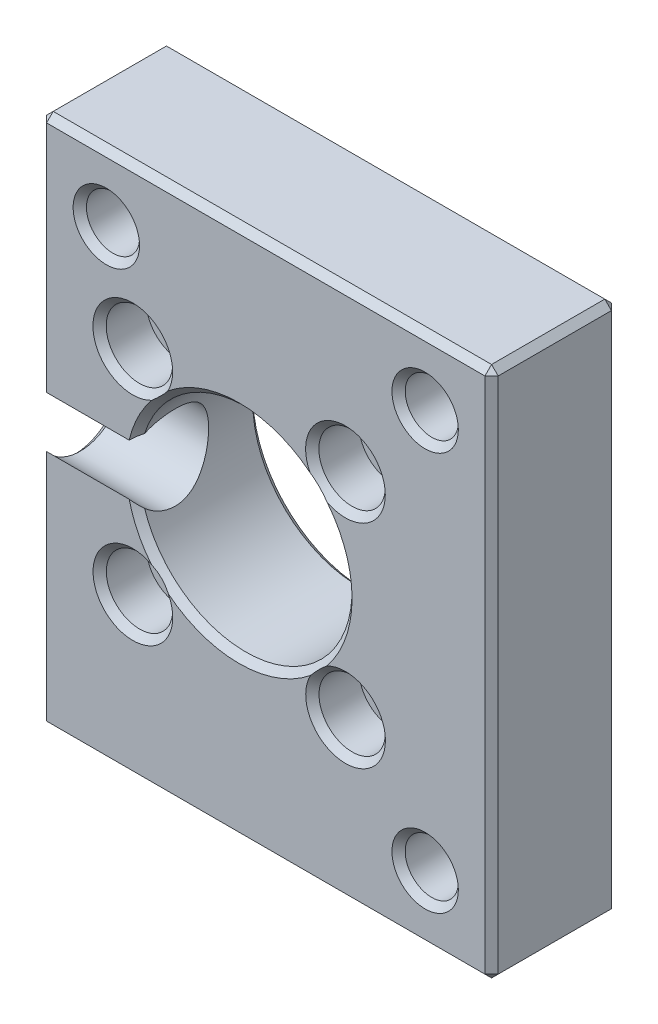
SolidWorks part; units mm, degrees
ref_plane "Front Plane" through (0, 0, 0) normal (0, 0, 1) x (1, 0, 0)
ref_plane "Top Plane" through (0, 0, 0) normal (0, 1, 0) x (1, 0, 0)
ref_plane "Right Plane" through (0, 0, 0) normal (1, 0, 0) x (0, 0, -1)
sketch "Sketch2" plane through (0, 0, 0) normal (0, 0, 1) x (1, 0, 0)
  line L0 (10, -8.01) -> (10, 8.01)
  line L1 (8.01, 10) -> (-8.01, 10)
  line L2 (-10, 8.01) -> (-10, -8.01)
  line L3 (-8.01, -10) -> (8.01, -10)
  line L5 (-11, 20) -> (19, 20)
  line L7 (-11, -20) -> (19, -20)
  line L8 (19, 20) -> (19, -20)
  line L9 (-11, -20) -> (-15, -20)
  line L11 (-11, 20) -> (-15, 20)
  line L12 (-15, -20) -> (-15, 20)
  arc A0 (10, 8.01) -> (8.01, 10) centre (8.01, 8.01) ccw
  arc A1 (-8.01, 10) -> (-10, 8.01) centre (-8.01, 8.01) ccw
  arc A2 (-10, -8.01) -> (-8.01, -10) centre (-8.01, -8.01) ccw
  arc A3 (8.01, -10) -> (10, -8.01) centre (8.01, -8.01) ccw
  circle A4 centre (8, -8) radius 1.25
  circle A5 centre (8, 8) radius 1.25
  circle A6 centre (-8, 8) radius 1.25
  circle A7 centre (-8, -8) radius 1.25
  circle A8 centre (0, 0) radius 8
  circle A9 centre (-10, 15) radius 3.9687
  circle A10 centre (14, 15) radius 3.9687
  circle A11 centre (14, -15) radius 3.9688
  circle A12 centre (-10, 15) radius 2
  circle A13 centre (14, 15) radius 2
  circle A14 centre (14, -15) radius 2
  circle A15 centre (-10, 15) radius 3.25
  circle A16 centre (14, -15) radius 3.25
  circle A17 centre (14, 15) radius 3.25
  dimension "D3" = 10
  dimension "D4" = 10
  dimension "D6" = 16
  dimension "D7" = 2.5
  dimension "D8" = 1.99
  dimension "D15" = 7.9375
  dimension "D16" = 4
  dimension "D17" = 7.9375
  dimension "D18" = 4
  dimension "D19" = 7.9375
  dimension "D20" = 4
  dimension "D21" = 6.5
  dimension "D22" = 6.5
  dimension "D23" = 6.5
  dimension "D24" = 34
  dimension "D1" = 40
  dimension "D2" = 30
  dimension "D5" = 16.02
  dimension "D9" = 8
  dimension "D10" = 19
  dimension "D11" = 8
  dimension "D12" = 8
  dimension "D13" = 20
  dimension "D14" = 8
  dimension "D25" = 5
  dimension "D26" = 5
  dimension "D27" = 5
  dimension "D28" = 29
  dimension "D29" = 5
  dimension "D30" = 5
extrude "Boss-Extrude1" add sketch "Sketch2" along normal blind 9.525
sketch "Sketch3" plane through (0, 0, 0) normal (0, 0, -1) x (-1, 0, 0)
  line L1 (11, 20) -> (-19, 20) construction
  line L2 (-19, 20) -> (-19, -20) construction
  line L3 (11, -20) -> (-19, -20) construction
  line L4 (-10, 8.01) -> (-10, -8.01)
  line L5 (8.01, 10) -> (-8.01, 10)
  line L6 (10, -8.01) -> (10, 8.01)
  line L7 (-8.01, -10) -> (8.01, -10)
  line L8 (-10, 8.01) -> (-10, -8.01)
  line L9 (8.01, 10) -> (-8.01, 10)
  line L10 (10, -8.01) -> (10, 8.01)
  line L11 (-8.01, -10) -> (8.01, -10)
  line L12 (11, 20) -> (-19, 20)
  line L13 (-19, 20) -> (-19, -20)
  line L14 (-19, -20) -> (11, -20)
  line L15 (11, -20) -> (15, -20)
  line L16 (11, 20) -> (-19, 20)
  line L17 (-19, 20) -> (-19, -20)
  line L18 (-19, -20) -> (11, -20)
  line L19 (11, -20) -> (15, -20)
  line L20 (11, -20) -> (15, -20) construction
  line L21 (15, -20) -> (15, 20) construction
  line L22 (11, 20) -> (15, 20) construction
  line L24 (-10, -8.01) -> (-10, 8.01) construction
  line L25 (-8.01, 10) -> (8.01, 10) construction
  line L26 (10, 8.01) -> (10, -8.01) construction
  line L27 (8.01, -10) -> (-8.01, -10) construction
  line L29 (11, 20) -> (-19, 20)
  line L30 (-19, 20) -> (-19, -20)
  line L31 (11, -20) -> (-19, -20)
  line L32 (11, -20) -> (15, -20)
  line L33 (15, -20) -> (15, 20)
  line L34 (11, 20) -> (15, 20)
  line L36 (-10, -8.01) -> (-10, 8.01)
  line L37 (-8.01, 10) -> (8.01, 10)
  line L38 (10, 8.01) -> (10, -8.01)
  line L39 (8.01, -10) -> (-8.01, -10)
  line L46 (15, -20) -> (15, 20)
  line L47 (15, -20) -> (15, 20)
  line L48 (15, 20) -> (11, 20)
  line L49 (15, 20) -> (11, 20)
  arc A0 (-8.01, 10) -> (-10, 8.01) centre (-8.01, 8.01) ccw construction
  circle A1 centre (-14, 15) radius 3.9687
  circle A2 centre (-14, 15) radius 3.9688
  circle A3 centre (10, 15) radius 3.9687
  arc A4 (-8.01, 10) -> (-10, 8.01) centre (-8.01, 8.01) ccw
  arc A5 (10, 8.01) -> (8.01, 10) centre (8.01, 8.01) ccw
  arc A6 (8.01, -10) -> (10, -8.01) centre (8.01, -8.01) ccw
  arc A7 (-10, -8.01) -> (-8.01, -10) centre (-8.01, -8.01) ccw
  arc A8 (-8.01, 10) -> (-10, 8.01) centre (-8.01, 8.01) ccw
  arc A9 (10, 8.01) -> (8.01, 10) centre (8.01, 8.01) ccw
  arc A10 (8.01, -10) -> (10, -8.01) centre (8.01, -8.01) ccw
  arc A11 (-10, -8.01) -> (-8.01, -10) centre (-8.01, -8.01) ccw
  circle A12 centre (10, 15) radius 3.9688
  circle A13 centre (0, 0) radius 8
  circle A14 centre (0, 0) radius 8
  circle A15 centre (8, -8) radius 1.25
  circle A16 centre (8, -8) radius 1.25
  circle A17 centre (8, 8) radius 1.25
  circle A18 centre (8, 8) radius 1.25
  circle A19 centre (-8, 8) radius 1.25
  circle A20 centre (-8, 8) radius 1.25
  circle A21 centre (-8, -8) radius 1.25
  circle A22 centre (-8, -8) radius 1.25
  circle A23 centre (-14, 15) radius 3.25
  circle A24 centre (-14, 15) radius 3.25
  circle A25 centre (-14, -15) radius 3.25
  circle A26 centre (-14, -15) radius 3.25
  circle A27 centre (10, 15) radius 3.25
  circle A28 centre (10, 15) radius 3.25
  circle A29 centre (-14, -15) radius 2
  circle A30 centre (-14, -15) radius 2
  circle A31 centre (-14, 15) radius 2
  circle A32 centre (-14, 15) radius 2
  circle A33 centre (10, 15) radius 2
  circle A34 centre (10, 15) radius 2
  circle A35 centre (-14, -15) radius 3.9688
  circle A36 centre (-14, -15) radius 3.9688
  arc A37 (10, 8.01) -> (8.01, 10) centre (8.01, 8.01) ccw construction
  arc A38 (8.01, -10) -> (10, -8.01) centre (8.01, -8.01) ccw construction
  arc A39 (-10, -8.01) -> (-8.01, -10) centre (-8.01, -8.01) ccw construction
  circle A40 centre (-14, 15) radius 3.9687 construction
  circle A41 centre (10, 15) radius 3.9687 construction
  circle A42 centre (0, 0) radius 8 construction
  circle A43 centre (8, -8) radius 1.25 construction
  circle A44 centre (8, 8) radius 1.25 construction
  circle A45 centre (-8, 8) radius 1.25 construction
  circle A46 centre (-8, -8) radius 1.25 construction
  circle A47 centre (-14, 15) radius 3.25 construction
  circle A48 centre (-14, -15) radius 3.25 construction
  circle A49 centre (10, 15) radius 3.25 construction
  circle A50 centre (-14, -15) radius 2 construction
  circle A51 centre (-14, 15) radius 2 construction
  circle A52 centre (10, 15) radius 2 construction
  circle A53 centre (-14, -15) radius 3.9688 construction
  arc A54 (-8.01, 10) -> (-10, 8.01) centre (-8.01, 8.01) ccw
  arc A55 (10, 8.01) -> (8.01, 10) centre (8.01, 8.01) ccw
  arc A56 (8.01, -10) -> (10, -8.01) centre (8.01, -8.01) ccw
  arc A57 (-10, -8.01) -> (-8.01, -10) centre (-8.01, -8.01) ccw
  circle A58 centre (-14, 15) radius 3.9688
  circle A59 centre (10, 15) radius 3.9688
  circle A60 centre (0, 0) radius 8
  circle A61 centre (8, -8) radius 1.25
  circle A62 centre (8, 8) radius 1.25
  circle A63 centre (-8, 8) radius 1.25
  circle A64 centre (-8, -8) radius 1.25
  circle A65 centre (-14, 15) radius 3.25
  circle A66 centre (-14, -15) radius 3.25
  circle A67 centre (10, 15) radius 3.25
  circle A68 centre (-14, -15) radius 2
  circle A69 centre (-14, 15) radius 2
  circle A70 centre (10, 15) radius 2
  circle A71 centre (-14, -15) radius 3.9688
  dimension "D1" = 0
  dimension "D2" = 0
  dimension "D3" = 0
  dimension "D4" = 0
  dimension "D5" = 0
  dimension "D6" = 0
  dimension "D7" = 0
  dimension "D8" = 0
  dimension "D9" = 0
  dimension "D10" = 0
  dimension "D11" = 0
  dimension "D12" = 0
  dimension "D13" = 0
  dimension "D14" = 0
  dimension "D15" = 0
  dimension "D16" = 0
extrude "Cut-Extrude1" cut sketch "Sketch3" against normal through all contours A14
sketch "Sketch4" plane through (0, 0, 9.525) normal (0, 0, 1) x (1, 0, 0)
  line L4 (19, -20) -> (19, 20)
  line L5 (19, 20) -> (-15, 20)
  line L6 (-15, 20) -> (-15, -20)
  line L7 (-15, -20) -> (19, -20)
  line L8 (19, -20) -> (19, 20)
  line L9 (19, 20) -> (-15, 20)
  line L11 (-15, -20) -> (19, -20)
  line L12 (10, -8.01) -> (10, 8.01)
  line L13 (8.01, 10) -> (-8.01, 10)
  line L14 (-10, 8.01) -> (-10, -8.01)
  line L15 (-8.01, -10) -> (8.01, -10)
  line L16 (10, -8.01) -> (10, 8.01)
  line L17 (8.01, 10) -> (-8.01, 10)
  line L18 (-10, 8.01) -> (-10, -8.01)
  line L19 (-8.01, -10) -> (8.01, -10)
  line L20 (19, 20) -> (-15, 20)
  line L21 (19, -20) -> (19, 20)
  line L22 (-15, -20) -> (19, -20)
  line L23 (-15, -20) -> (-11, -20)
  line L24 (19, 20) -> (-15, 20)
  line L25 (19, -20) -> (19, 20)
  line L26 (-15, -20) -> (19, -20)
  line L28 (-15, 20) -> (-15, -20)
  line L31 (-15, -20) -> (-11, -20)
  line L32 (-15, 20) -> (-15, -20)
  line L33 (-15, 20) -> (-15, -20)
  line L34 (-11, 20) -> (-15, 20)
  line L35 (-11, 20) -> (-15, 20)
  circle A0 centre (-8, -8) radius 2.5
  circle A1 centre (14, 15) radius 3.9687
  circle A2 centre (14, 15) radius 3.9688
  circle A3 centre (-10, 15) radius 3.9687
  arc A4 (10, 8.01) -> (8.01, 10) centre (8.01, 8.01) ccw
  arc A5 (-8.01, 10) -> (-10, 8.01) centre (-8.01, 8.01) ccw
  arc A6 (-10, -8.01) -> (-8.01, -10) centre (-8.01, -8.01) ccw
  arc A7 (8.01, -10) -> (10, -8.01) centre (8.01, -8.01) ccw
  arc A8 (10, 8.01) -> (8.01, 10) centre (8.01, 8.01) ccw
  arc A9 (-8.01, 10) -> (-10, 8.01) centre (-8.01, 8.01) ccw
  arc A10 (-10, -8.01) -> (-8.01, -10) centre (-8.01, -8.01) ccw
  arc A11 (8.01, -10) -> (10, -8.01) centre (8.01, -8.01) ccw
  circle A12 centre (-10, 15) radius 3.9688
  circle A13 centre (0, 0) radius 8
  circle A14 centre (0, 0) radius 8
  circle A15 centre (-8, -8) radius 1.25
  circle A16 centre (-8, -8) radius 1.25
  circle A17 centre (-8, 8) radius 1.25
  circle A18 centre (-8, 8) radius 1.25
  circle A19 centre (8, 8) radius 1.25
  circle A20 centre (8, 8) radius 1.25
  circle A21 centre (8, -8) radius 1.25
  circle A22 centre (8, -8) radius 1.25
  circle A23 centre (14, 15) radius 3.25
  circle A24 centre (14, 15) radius 3.25
  circle A25 centre (14, -15) radius 3.25
  circle A26 centre (14, -15) radius 3.25
  circle A27 centre (-10, 15) radius 3.25
  circle A28 centre (-10, 15) radius 3.25
  circle A29 centre (14, -15) radius 2
  circle A30 centre (14, -15) radius 2
  circle A31 centre (14, 15) radius 2
  circle A32 centre (14, 15) radius 2
  circle A33 centre (-10, 15) radius 2
  circle A34 centre (-10, 15) radius 2
  circle A35 centre (14, -15) radius 3.9688
  circle A36 centre (14, -15) radius 3.9688
  circle A37 centre (-8.01, 8.01) radius 2.5
  circle A38 centre (8, 8) radius 2.5
  circle A39 centre (8.01, -8.01) radius 2.5
  circle M9 centre (-8, -8) radius 1.25
  circle M10 centre (-8, 8) radius 1.25
  circle M11 centre (8, 8) radius 1.25
  circle M12 centre (8, -8) radius 1.25
  dimension "D18" = 5
  dimension "D19" = 5
  dimension "D20" = 5
  dimension "D21" = 5
  dimension "D1" = 0
  dimension "D2" = 0
  dimension "D3" = 0
  dimension "D4" = 0
  dimension "D5" = 0
  dimension "D6" = 0
  dimension "D7" = 0
  dimension "D8" = 0
  dimension "D9" = 0
  dimension "D10" = 0
  dimension "D11" = 0
  dimension "D12" = 0
  dimension "D13" = 0
  dimension "D14" = 0
  dimension "D15" = 0
  dimension "D16" = 0
  dimension "D17" = 0
sketch "Sketch9" plane through (-15, 0, 0) normal (-1, 0, 0) x (0, 0, 1)
  line L0 (0, -20) -> (0, 20) construction
  circle A0 centre (7, 0) radius 3.175
  dimension "D2" = 6.35
  dimension "D1" = 7
extrude "Cut-Extrude8" cut sketch "Sketch9" against normal blind 15
extrude "Cut-Extrude5" cut sketch "Sketch4" against normal blind 3.525 contours L17 A37 L18 A9 | L18 A37 L17 A9 M10 | L17 A38 L16 A8 M11 | L16 A38 L17 A8 | A10 L18 A0 L19 | L18 A10 L19 A0 M9 | L19 A39 L16 A11 | L16 A39 L19 A11 M12 | A20
sketch "Sketch7" plane through (0, 0, 9.525) normal (0, 0, 1) x (1, 0, 0)
  line L1 (-15, -20) -> (19, -20) construction
  line L2 (-15, -20) -> (19, -20) construction
  line L4 (19, 20) -> (-15, 20) construction
  line L5 (19, 20) -> (-15, 20) construction
  line L6 (19, -20) -> (19, 20) construction
  line L7 (-15, -1.9248) -> (-15, -20)
  line L8 (-15, -1.9248) -> (-15, -20)
  line L10 (-15, -20) -> (19, -20)
  line L11 (19, -20) -> (19, 20)
  line L12 (19, 20) -> (-15, 20)
  line L17 (-15, -20) -> (19, -20)
  line L18 (19, -20) -> (19, 20)
  line L19 (19, 20) -> (-15, 20)
  line L21 (19, -20) -> (19, 20) construction
  line L22 (10, -8.01) -> (10, 8.01) construction
  line L23 (8.01, 10) -> (-8.01, 10) construction
  line L24 (-10, 8.01) -> (-10, -8.01) construction
  line L25 (-8.01, -10) -> (8.01, -10) construction
  line L27 (-15, -20) -> (19, -20)
  line L28 (-15, -20) -> (19, -20)
  line L30 (19, 20) -> (-15, 20)
  line L31 (19, 20) -> (-15, 20)
  line L32 (19, -20) -> (19, 20)
  line L33 (19, -20) -> (19, 20)
  line L34 (10, -8.01) -> (10, 8.01)
  line L35 (8.01, 10) -> (-8.01, 10)
  line L36 (-10, 8.01) -> (-10, -8.01)
  line L37 (-8.01, -10) -> (8.01, -10)
  line L39 (-15, 1.9248) -> (-7.765, 1.9248)
  line L40 (-15, 1.9248) -> (-7.765, 1.9248)
  line L41 (-7.765, -1.9248) -> (-15, -1.9248)
  line L42 (-7.765, -1.9248) -> (-15, -1.9248)
  line L43 (-15, 20) -> (-15, 1.9248)
  line L44 (-15, 20) -> (-15, 1.9248)
  arc A0 (10, 8.01) -> (8.01, 10) centre (8.01, 8.01) ccw construction
  arc A2 (-7.765, -1.9248) -> (-7.765, 1.9248) centre (0, 0) ccw
  arc A3 (-8.01, 10) -> (-10, 8.01) centre (-8.01, 8.01) ccw construction
  arc A4 (-10, -8.01) -> (-8.01, -10) centre (-8.01, -8.01) ccw construction
  arc A5 (8.01, -10) -> (10, -8.01) centre (8.01, -8.01) ccw construction
  circle A6 centre (-8, -8) radius 1.25 construction
  circle A7 centre (0, 0) radius 8 construction
  circle A8 centre (-10, 15) radius 3.9688 construction
  circle A9 centre (14, 15) radius 3.9688 construction
  circle A10 centre (-10, 15) radius 3.25 construction
  circle A11 centre (14, -15) radius 3.25 construction
  circle A12 centre (14, 15) radius 3.25 construction
  circle A13 centre (8, -8) radius 1.25 construction
  circle A14 centre (8, 8) radius 1.25 construction
  circle A15 centre (-8, 8) radius 1.25 construction
  circle A16 centre (8.01, -8.01) radius 2.5 construction
  circle A17 centre (8, 8) radius 2.5 construction
  circle A18 centre (-8.01, 8.01) radius 2.5 construction
  circle A19 centre (14, -15) radius 3.9688 construction
  circle A20 centre (-10, 15) radius 2 construction
  circle A21 centre (14, 15) radius 2 construction
  circle A22 centre (14, -15) radius 2 construction
  circle A23 centre (-8, -8) radius 2.5 construction
  arc A24 (10, 8.01) -> (8.01, 10) centre (8.01, 8.01) ccw
  arc A25 (-8.01, 10) -> (-10, 8.01) centre (-8.01, 8.01) ccw
  arc A26 (-10, -8.01) -> (-8.01, -10) centre (-8.01, -8.01) ccw
  arc A27 (8.01, -10) -> (10, -8.01) centre (8.01, -8.01) ccw
  circle A28 centre (-8, -8) radius 1.25
  circle A29 centre (0, 0) radius 8
  circle A30 centre (-10, 15) radius 3.9688
  circle A31 centre (14, 15) radius 3.9688
  circle A32 centre (-10, 15) radius 3.25
  circle A33 centre (14, -15) radius 3.25
  circle A34 centre (14, 15) radius 3.25
  circle A35 centre (8, -8) radius 1.25
  circle A36 centre (8, 8) radius 1.25
  circle A37 centre (-8, 8) radius 1.25
  circle A38 centre (8.01, -8.01) radius 2.5
  circle A39 centre (8, 8) radius 2.5
  circle A40 centre (-8.01, 8.01) radius 2.5
  circle A41 centre (14, -15) radius 3.9688
  circle A42 centre (-10, 15) radius 2
  circle A43 centre (14, 15) radius 2
  circle A44 centre (14, -15) radius 2
  circle A45 centre (-8, -8) radius 2.5
  arc A46 (-7.765, -1.9248) -> (-7.765, 1.9248) centre (0, 0) ccw
  dimension "D1" = 0
extrude "Cut-Extrude6" cut sketch "Sketch7" against normal through all contours A42 | A43 | A44
sketch "Sketch8" plane through (0, 0, 0) normal (0, 0, -1) x (-1, 0, 0)
  line L4 (-10, 8.01) -> (-10, -8.01)
  line L5 (8.01, 10) -> (-8.01, 10)
  line L6 (10, -8.01) -> (10, 8.01)
  line L7 (-8.01, -10) -> (8.01, -10)
  line L8 (-10, 8.01) -> (-10, -8.01)
  line L9 (8.01, 10) -> (-8.01, 10)
  line L10 (10, -8.01) -> (10, 8.01)
  line L11 (-8.01, -10) -> (8.01, -10)
  line L12 (11, 20) -> (-19, 20)
  line L13 (-19, 20) -> (-19, -20)
  line L14 (-19, -20) -> (11, -20)
  line L15 (11, -20) -> (15, -20)
  line L16 (11, 20) -> (-19, 20)
  line L17 (-19, 20) -> (-19, -20)
  line L18 (-19, -20) -> (11, -20)
  line L19 (11, -20) -> (15, -20)
  line L22 (15, -20) -> (15, 20)
  line L23 (15, -20) -> (15, 20)
  line L24 (15, 20) -> (11, 20)
  line L25 (15, 20) -> (11, 20)
  circle A1 centre (-14, 15) radius 3.9687
  circle A2 centre (-14, 15) radius 3.9688
  circle A3 centre (10, 15) radius 3.9687
  arc A4 (-8.01, 10) -> (-10, 8.01) centre (-8.01, 8.01) ccw
  arc A5 (10, 8.01) -> (8.01, 10) centre (8.01, 8.01) ccw
  arc A6 (8.01, -10) -> (10, -8.01) centre (8.01, -8.01) ccw
  arc A7 (-10, -8.01) -> (-8.01, -10) centre (-8.01, -8.01) ccw
  arc A8 (-8.01, 10) -> (-10, 8.01) centre (-8.01, 8.01) ccw
  arc A9 (10, 8.01) -> (8.01, 10) centre (8.01, 8.01) ccw
  arc A10 (8.01, -10) -> (10, -8.01) centre (8.01, -8.01) ccw
  arc A11 (-10, -8.01) -> (-8.01, -10) centre (-8.01, -8.01) ccw
  circle A12 centre (10, 15) radius 3.9688
  circle A13 centre (0, 0) radius 8
  circle A14 centre (0, 0) radius 8
  circle A15 centre (8, -8) radius 1.25
  circle A16 centre (8, -8) radius 1.25
  circle A17 centre (8, 8) radius 1.25
  circle A18 centre (8, 8) radius 1.25
  circle A19 centre (-8, 8) radius 1.25
  circle A20 centre (-8, 8) radius 1.25
  circle A21 centre (-8, -8) radius 1.25
  circle A22 centre (-8, -8) radius 1.25
  circle A23 centre (-14, 15) radius 3.25
  circle A24 centre (-14, 15) radius 3.25
  circle A25 centre (-14, -15) radius 3.25
  circle A26 centre (-14, -15) radius 3.25
  circle A27 centre (10, 15) radius 3.25
  circle A28 centre (10, 15) radius 3.25
  circle A29 centre (-14, -15) radius 2
  circle A30 centre (-14, -15) radius 2
  circle A31 centre (-14, 15) radius 2
  circle A32 centre (-14, 15) radius 2
  circle A33 centre (10, 15) radius 2
  circle A34 centre (10, 15) radius 2
  circle A35 centre (-14, -15) radius 3.9688
  circle A36 centre (-14, -15) radius 3.9688
  circle M27 centre (-14, -15) radius 2
  circle M28 centre (-14, 15) radius 2
  circle M29 centre (10, 15) radius 2
  dimension "D1" = 0
  dimension "D2" = 0
  dimension "D3" = 0
  dimension "D4" = 0
  dimension "D5" = 0
  dimension "D6" = 0
  dimension "D7" = 0
  dimension "D8" = 0
  dimension "D9" = 0
  dimension "D10" = 0
  dimension "D11" = 0
  dimension "D12" = 0
  dimension "D13" = 0
  dimension "D14" = 0
  dimension "D15" = 0
  dimension "D16" = 0
extrude "Cut-Extrude7" cut sketch "Sketch8" against normal blind 5.525 contours A26 M27 | A28 M29 | A24 M28
chamfer "Chamfer1" distance 0.5 angle 45 30 edges at (16, -15, 9.525) (10.51, -8.01, 9.525) (-5.5, -8, 9.525) (8, 0, 9.525) (10.5, 8, 9.525) (-5.51, 8.01, 9.525) (-8, 15, 9.525) (16, 15, 9.525) (-13.25, 15, 0) (10.75, 15, 0) (9.25, 8, 0) (-6.75, 8, 0) (-8, 0, 0) (-6.75, -8, 0) (10.75, -15, 0) (9.25, -8, 0) (2, 20, 0) (2, 20, 9.525) (19, 0, 0) (19, 0, 9.525) (19, 20, 4.7625) (-15, 20, 4.7625) (-15, 0, 0) (19, -20, 4.7625) (2, -20, 0) (2, -20, 9.525) (-15, -20, 4.7625) (-15, 10.9624, 9.525) (-15, 0, 3.825) (-15, -10.9624, 9.525)
